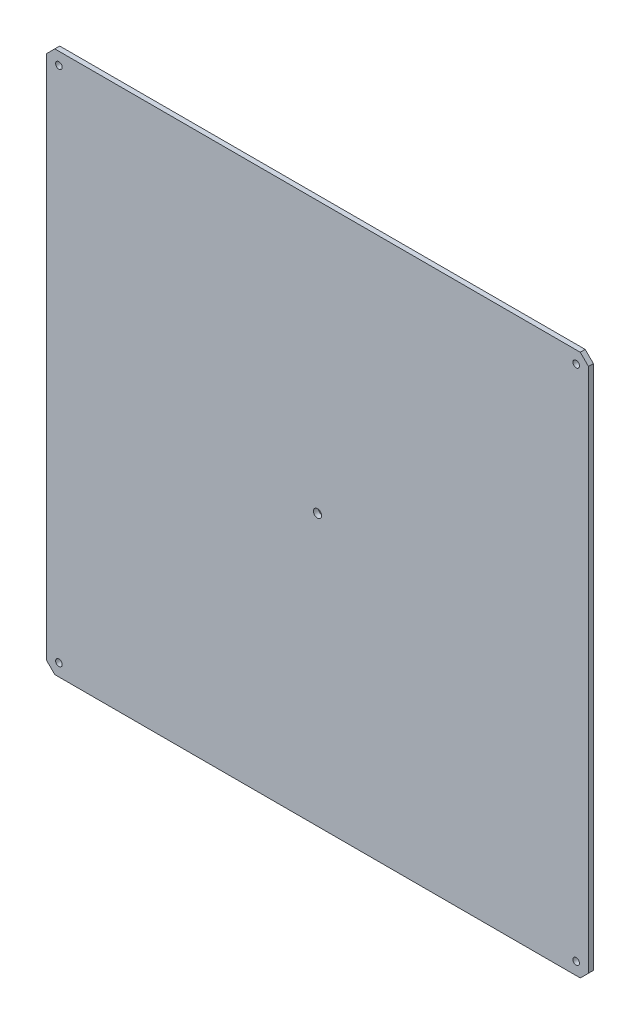
SolidWorks part; units mm, degrees
ref_plane "Front Plane" through (0, 0, 0) normal (0, 0, 1) x (1, 0, 0)
ref_plane "Top Plane" through (0, 0, 0) normal (0, 1, 0) x (1, 0, 0)
ref_plane "Right Plane" through (0, 0, 0) normal (1, 0, 0) x (0, 0, -1)
sketch "Sketch1" plane through (0, 0, 0) normal (0, 0, 1) x (1, 0, 0)
  line L1 (-165, 165) -> (165, 165)
  line L2 (-165, 165) -> (-165, -165)
  line L3 (-165, -165) -> (165, -165)
  line L4 (165, 165) -> (165, -165)
  line L5 (-165, 165) -> (165, -165) construction
  line L6 (-165, -165) -> (165, 165) construction
  circle A0 centre (-157.5, 157.5) radius 2
  circle A1 centre (157.5, 157.5) radius 2
  circle A2 centre (157.5, -157.5) radius 2
  circle A3 centre (-157.5, -157.5) radius 2
  circle A4 centre (0, 0) radius 2.5
  point P0 (0, 0)
  dimension "D2" = 4
  dimension "D7" = 5
  dimension "D1" = 330
  dimension "D3" = 7.5
  dimension "D4" = 7.5
  dimension "D5" = 7.5
  dimension "D6" = 7.5
extrude "Boss-Extrude1" add sketch "Sketch1" along normal blind 3
chamfer "Chamfer1" distance 5 angle 45 4 edges at (-165, -165, 1.5) (165, -165, 1.5) (165, 165, 1.5) (-165, 165, 1.5)
